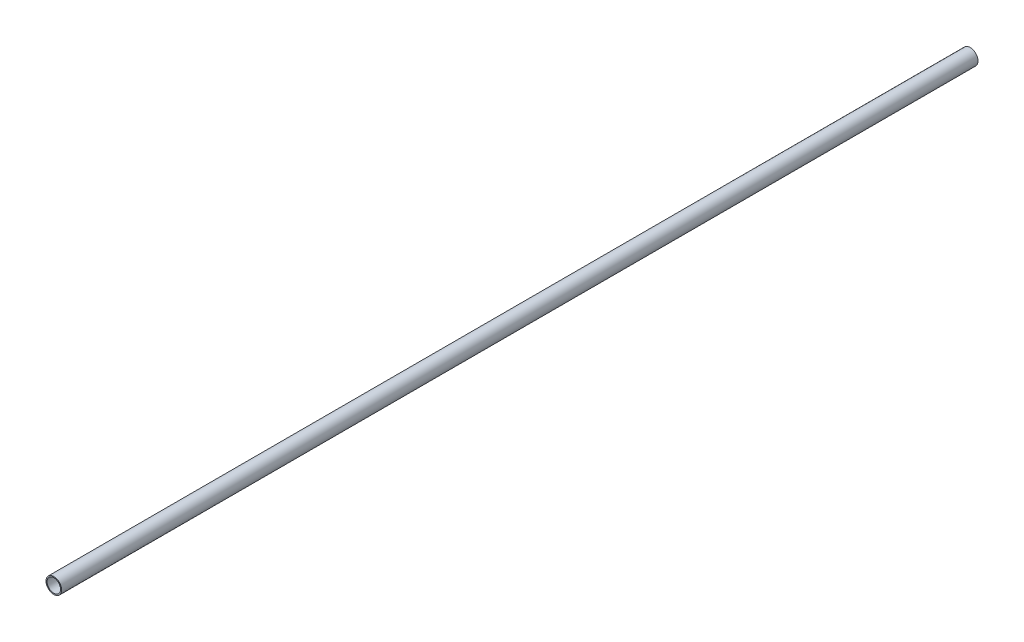
SolidWorks part; units mm, degrees
material "McMaster Carbon Fiber Twill Tube"
ref_plane "Front Plane" through (0, 0, 0) normal (0, 0, 1) x (1, 0, 0)
ref_plane "Top Plane" through (0, 0, 0) normal (0, 1, 0) x (1, 0, 0)
ref_plane "Right Plane" through (0, 0, 0) normal (1, 0, 0) x (0, 0, -1)
sketch "Sketch1" plane through (0, 0, 0) normal (0, 0, 1) x (1, 0, 0)
  circle A0 centre (0, 0) radius 10.922 construction
  circle A1 centre (0, 0) radius 12.7 construction
  point P4 (12.7, 0)
  point P5 (10.922, 0)
  dimension "OD" = 21.844
  dimension "ID" = 25.4
  dimension "Wall Thickness" = 1.778
sketch "Sketch2" plane through (0, 0, 0) normal (1, 0, 0) x (0, 0, -1)
  line L0 (-742.95, 0) -> (742.95, 0) construction
  line L1 (-742.95, -10.922) -> (-742.95, 10.922) construction
  line L2 (-742.95, 10.922) -> (742.95, 10.922) construction
  line L3 (742.95, -10.922) -> (742.95, 10.922) construction
  line L5 (-742.95, -10.922) -> (742.95, -10.922) construction
  point P0 (-721.106, 0)
  point P3 (0, 0)
  point P7 (0, 10.922)
  point P8 (721.106, 0)
  point P11 (-742.95, 0)
  point P13 (742.95, 0)
  dimension "Length" = 1485.9
  dimension "D1" = 21.844
  dimension "D2" = 21.844
sketch "Sketch3" plane through (0, 0, 0) normal (0, 0, 1) x (1, 0, 0)
  circle A0 centre (0, 0) radius 12.7 construction
  circle A1 centre (0, 0) radius 10.922 construction
  circle A2 centre (0, 0) radius 12.7
  circle A3 centre (0, 0) radius 10.922
extrude "Boss-Extrude1" add sketch "Sketch3" along normal up to vertex (742.95 mm away) and the other way up to vertex (742.95 mm away) up to point (0, 0, 742.95) other way up to point (0, 0, -742.95)
equation "\"D1@Sketch2\"=\"OD@Sketch1\""
equation "\"D2@Sketch2\"=\"D1@Sketch2\""
